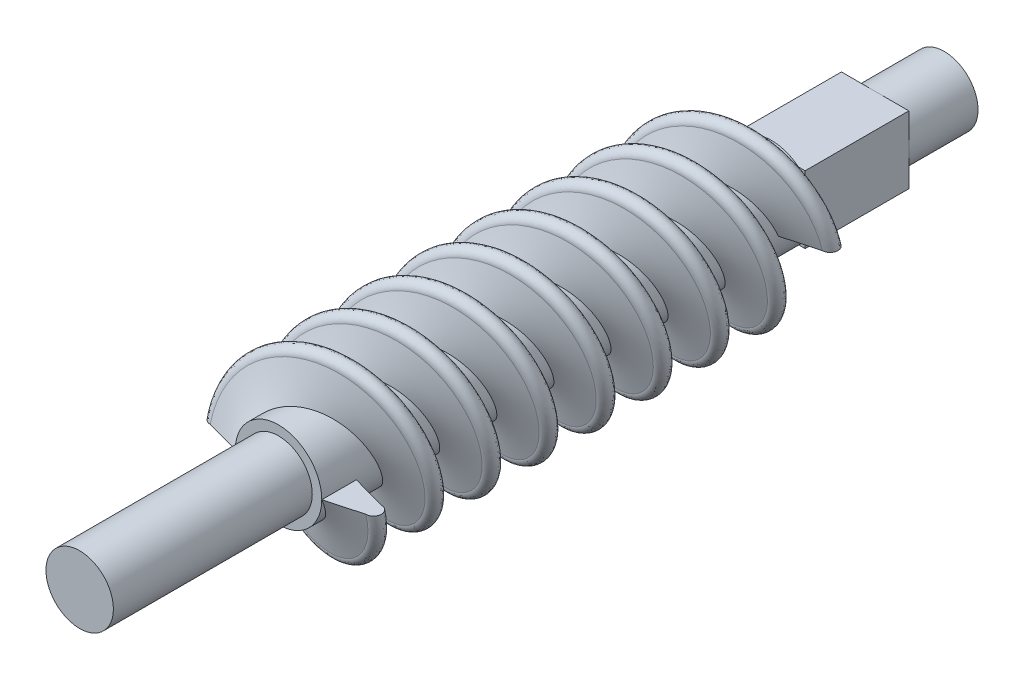
SolidWorks part; units mm, degrees
ref_plane "Plan de face" through (0, 0, 0) normal (0, 0, 1) x (1, 0, 0)
ref_plane "Plan de dessus" through (0, 0, 0) normal (0, 1, 0) x (1, 0, 0)
ref_plane "Plan de droite" through (0, 0, 0) normal (1, 0, 0) x (0, 0, -1)
sketch "Esquisse1" plane through (0, 0, 0) normal (0, 0, 1) x (1, 0, 0)
  circle A0 centre (0, 0) radius 5
  dimension "D1" = 10
extrude "Boss.-Extru.1" add sketch "Esquisse1" along normal blind 55
sketch "Esquisse3" plane through (0, 0, 55) normal (0, 0, 1) x (1, 0, 0)
  circle A0 centre (0, 0) radius 5
curve "Hélice/Spirale1" pitch 13.2 height 52.8 turns 4
sketch "Esquisse4" plane through (0, 0, 0) normal (0, 1, 0) x (1, 0, 0)
  line L0 (-5, -55) -> (-9, -55) construction
  line L1 (-5, 0) -> (-5, -55) construction
  line L2 (-9, -54.1) -> (-5, -53)
  line L3 (-9, -55.9) -> (-5, -57)
  line L5 (-5, -53) -> (-4.702, -53)
  line L6 (-4.702, -53) -> (-4.702, -57)
  line L7 (-4.702, -57) -> (-5, -57)
  arc A1 (-9, -54.1) -> (-9, -55.9) centre (-9, -55) ccw
  spline S0 degree 3 poles (-5, -55) (-5, -54.7265) (-4.7397, -54.1743) (-3.6276, -53.3502) (-1.9632, -52.525) (0, -51.7) (1.9632, -50.875) (3.6276, -50.05) (4.7397, -49.225) (5.1302, -48.4) (4.7397, -47.575) (3.6276, -46.75) (1.4084, -45.65) (-1.4084, -44.55) (-3.6276, -43.45) (-4.7397, -42.625) (-5.1302, -41.8) (-4.7397, -40.975) (-3.6276, -40.15) (-1.4084, -39.05) (1.4084, -37.95) (3.6276, -36.85) (4.7397, -36.025) (5.1302, -35.2) (4.7397, -34.375) (3.6276, -33.55) (1.4084, -32.45) (-1.4084, -31.35) (-3.6276, -30.25) (-4.7397, -29.425) (-5.1302, -28.6) (-4.7397, -27.775) (-3.6276, -26.95) (-1.4084, -25.85) (1.4084, -24.75) (3.6276, -23.65) (4.7397, -22.825) (5.1302, -22) (4.7397, -21.175) (3.6276, -20.35) (1.4084, -19.25) (-1.4084, -18.15) (-3.6276, -17.05) (-4.7397, -16.225) (-5.1302, -15.4) (-4.7397, -14.575) (-3.6276, -13.75) (-1.4084, -12.65) (1.4084, -11.55) (3.6276, -10.45) (4.7397, -9.625) (5.1302, -8.8) (4.7397, -7.975) (3.6276, -7.15) (1.9632, -6.325) (0, -5.5) (-1.9632, -4.675) (-3.6276, -3.8498) (-4.7397, -3.0257) (-5, -2.4735) (-5, -2.2) knots 0 0 0 0 0.015625 0.03125 0.046875 0.0625 0.078125 0.09375 0.109375 0.125 0.140625 0.15625 0.171875 0.203125 0.21875 0.234375 0.25 0.265625 0.28125 0.296875 0.328125 0.34375 0.359375 0.375 0.390625 0.40625 0.421875 0.453125 0.46875 0.484375 0.5 0.515625 0.53125 0.546875 0.578125 0.59375 0.609375 0.625 0.640625 0.65625 0.671875 0.703125 0.71875 0.734375 0.75 0.765625 0.78125 0.796875 0.828125 0.84375 0.859375 0.875 0.890625 0.90625 0.921875 0.9375 0.953125 0.96875 0.984375 1 1 1 1 construction
  dimension "D3" = 0.9
  dimension "D1" = 4
  dimension "D2" = 4
sweep "Balayage2" add profiles "Esquisse4" path "Hélice/Spirale1"
pattern_circular "CirPattern1" count 2 over 360 about axis through (0, 0, 55) along (0, 0, -1) of "Balayage2"
sketch "arbre" plane through (0, 0, 0) normal (0, 0, -1) x (-1, 0, 0)
  line L1 (-3.9, 3.9) -> (3.9, 3.9)
  line L2 (-3.9, 3.9) -> (-3.9, -3.9)
  line L3 (-3.9, -3.9) -> (3.9, -3.9)
  line L4 (3.9, 3.9) -> (3.9, -3.9)
  line L5 (-3.9, 3.9) -> (3.9, -3.9) construction
  line L6 (-3.9, -3.9) -> (3.9, 3.9) construction
  point P0 (0, 0)
  dimension "D1" = 7.8
  dimension "D2" = 7.8
sketch "Sketch1" plane through (0, 0, 55) normal (0, 0, 1) x (1, 0, 0)
  circle A0 centre (0, 0) radius 3.9
  dimension "D1" = 7.8
extrude "Bearing-side" add sketch "Sketch1" along normal blind 25
sketch "Sketch2" plane through (0, 0, 55) normal (0, 0, 1) x (1, 0, 0)
  circle A0 centre (0, 0) radius 5
  dimension "D1" = 10
extrude "Boss-Extrude2" add sketch "Sketch2" along normal blind 2
extrude "Boss-Extrude3" add sketch "arbre" along normal blind 12 contours L3 L4 L1 L2
sketch "Sketch4" plane through (0, 0, -12) normal (0, 0, -1) x (-1, 0, 0)
  circle A0 centre (0, 0) radius 3.9
  dimension "D1" = 7.8
extrude "Boss-Extrude4" add sketch "Sketch4" along normal blind 8
